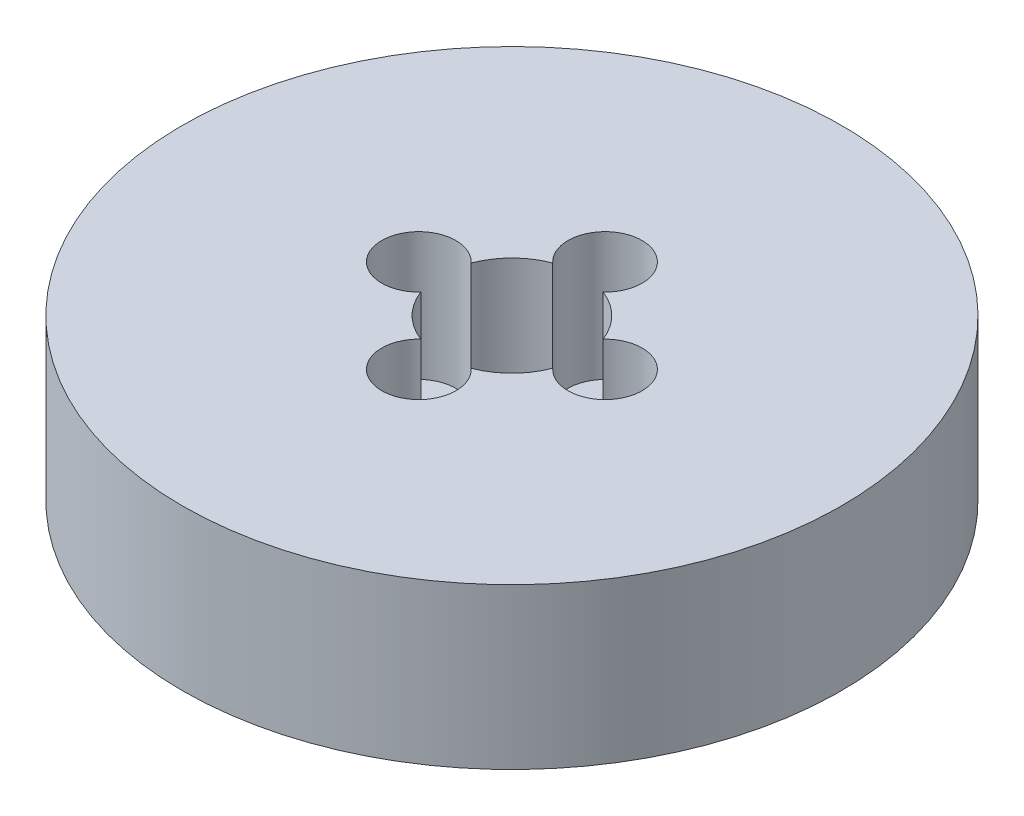
SolidWorks part; units mm, degrees
ref_plane "Front Plane" through (0, 0, 0) normal (0, 0, 1) x (1, 0, 0)
ref_plane "Top Plane" through (0, 0, 0) normal (0, 1, 0) x (1, 0, 0)
ref_plane "Right Plane" through (0, 0, 0) normal (1, 0, 0) x (0, 0, -1)
sketch "Sketch1" plane through (0, 0, 0) normal (0, 1, 0) x (1, 0, 0)
  circle A0 centre (0, 0) radius 35
  dimension "FLANGE_OD" = 70
extrude "Boss-Extrude1" add sketch "Sketch1" along normal blind 17
sketch "Sketch2" plane through (0, 0, 0) normal (0, 1, 0) x (1, 0, 0)
  circle A0 centre (0, 0) radius 7.5
  dimension "BORE_D" = 15
extrude "Cut-Extrude1" cut sketch "Sketch2" along normal through all
sketch "Sketch3" plane through (0, 17, 0) normal (0, 1, 0) x (1, 0, 0)
  circle A0 centre (0, 0) radius 9.8893 construction
  circle A1 centre (-9.8893, 0) radius 3.9346
  dimension "BOLT_D" = 7.8693
  dimension "BOLT_PCD" = 19.7786
extrude "Cut-Extrude2" cut sketch "Sketch3" against normal blind 13.5981
pattern_circular "CirPattern1" count 4 over 360 about axis through (0, 0, 0) along (0, 1, 0) of "Cut-Extrude2"
